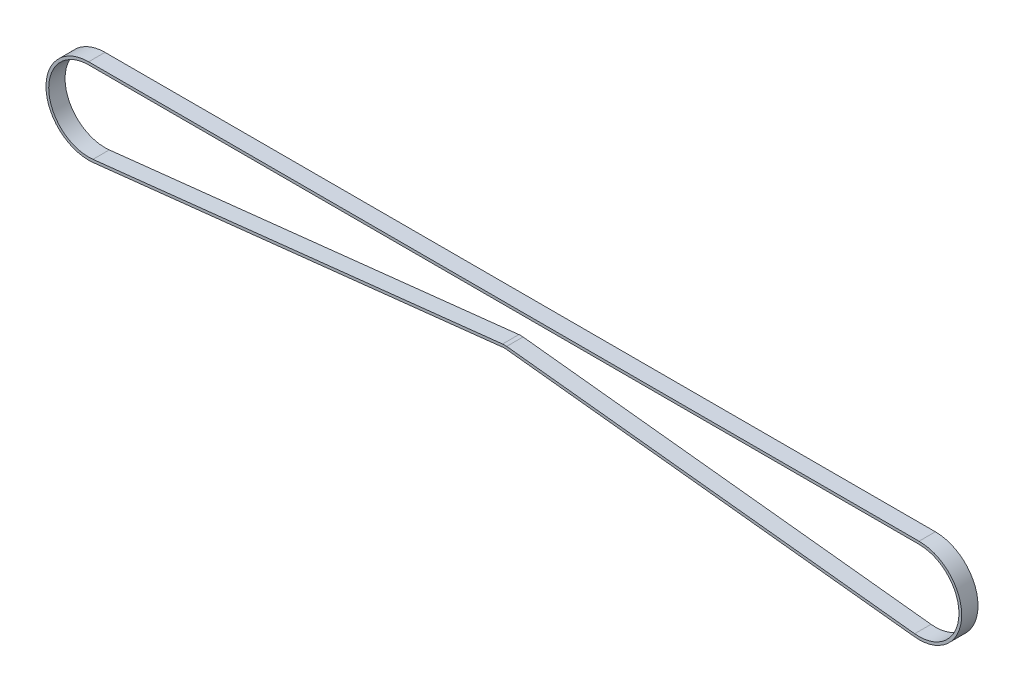
SolidWorks part; units mm, degrees
material "Caucho"
ref_plane "Alzado" through (0, 0, 0) normal (0, 0, 1) x (1, 0, 0)
ref_plane "Planta" through (0, 0, 0) normal (0, 1, 0) x (1, 0, 0)
ref_plane "Vista lateral" through (0, 0, 0) normal (1, 0, 0) x (0, 0, -1)
sketch "Croquis1" plane through (0, 0, 0) normal (0, 0, 1) x (1, 0, 0)
  line L0 (0, 0) -> (305, 0) construction
  line L1 (0, 15.66) -> (305, 15.66)
  line L3 (1.7051, -15.5669) -> (152.1359, 0.9103)
  line L4 (303.2884, -15.5662) -> (153.445, 0.91)
  line L10 (-22.5, -22.5) -> (327.5, -22.5) construction
  line L11 (-22.5, -22.5) -> (-22.5, 22.5) construction
  line L12 (-22.5, 22.5) -> (327.5, 22.5) construction
  line L13 (327.5, -22.5) -> (327.5, 22.5) construction
  line L14 (-22.5, -22.5) -> (327.5, 22.5) construction
  line L15 (-22.5, 22.5) -> (327.5, -22.5) construction
  line L18 (0, 14.66) -> (305, 14.66)
  line L19 (303.3977, -14.5722) -> (153.5543, 1.904)
  line L20 (1.5962, -14.5728) -> (152.027, 1.9044)
  arc A0 (0, 15.66) -> (1.7051, -15.5669) centre (0, 0) ccw
  arc A1 (303.2884, -15.5662) -> (305, 15.66) centre (305, 0) ccw
  arc A2 (153.445, 0.91) -> (152.1359, 0.9103) centre (152.7892, -5.054) ccw
  circle A3 centre (152.7892, -5.054) radius 6 construction
  arc A7 (303.3977, -14.5722) -> (305, 14.66) centre (305, 0) ccw
  arc A8 (153.5543, 1.904) -> (152.027, 1.9044) centre (152.7892, -5.054) ccw
  arc A9 (0, 14.66) -> (1.5962, -14.5728) centre (0, 0) ccw
  point P1 (152.5, 0)
  dimension "D2" = 31.32
  dimension "D3" = 31.32
  dimension "D6" = 12
  dimension "D1" = 305
  dimension "D4" = 305
  dimension "D5" = 350
  dimension "D7" = 45
  dimension "D8" = 1
extrude "Saliente-Extruir1" add sketch "Croquis1" along normal blind 6
